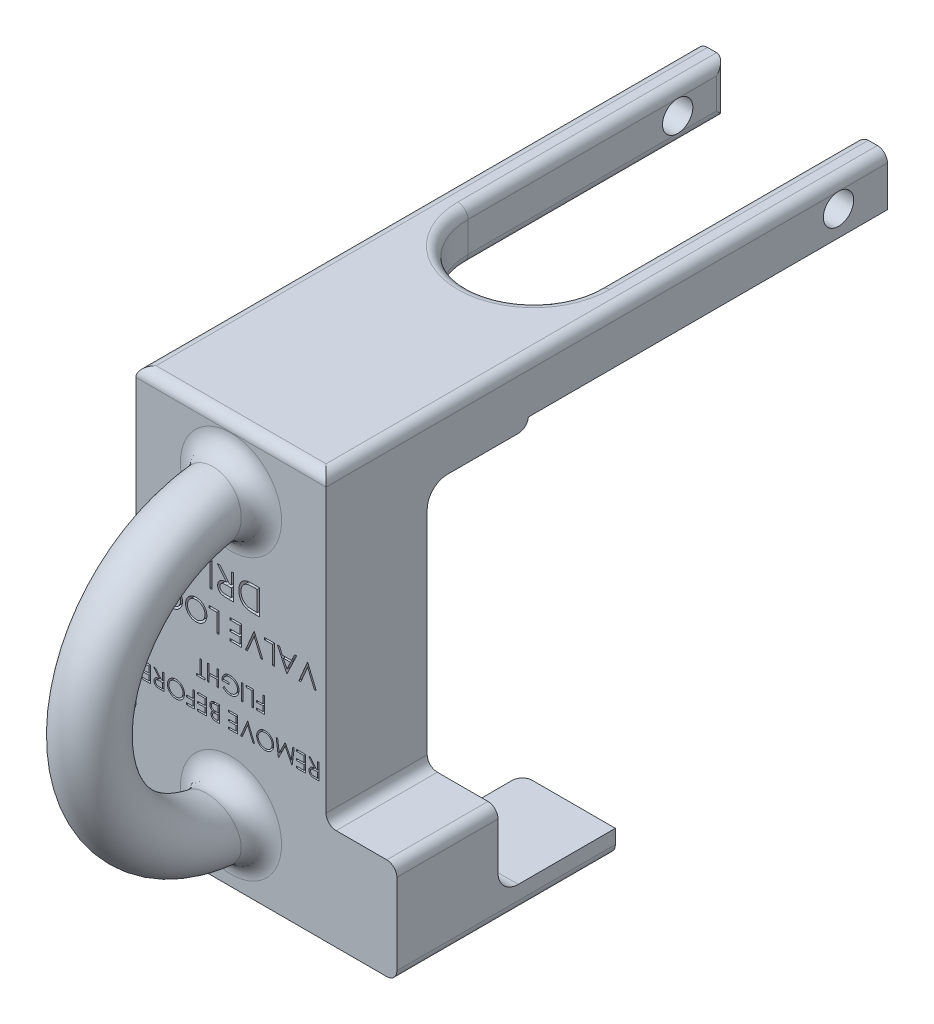
SolidWorks part; units mm, degrees
material "ABS PC"
ref_plane "Front Plane" through (0, 0, 0) normal (0, 0, 1) x (1, 0, 0)
ref_plane "Top Plane" through (0, 0, 0) normal (0, 1, 0) x (1, 0, 0)
ref_plane "Right Plane" through (0, 0, 0) normal (1, 0, 0) x (0, 0, -1)
sketch "Sketch1" plane through (0, 0, 0) normal (0, 0, 1) x (1, 0, 0)
  line L0 (0, 2.5) -> (0, -5) construction
  line L1 (-11.938, -5) -> (11.938, -5)
  line L2 (-11.938, -5) -> (-11.938, 2.5)
  line L3 (-11.938, 2.5) -> (11.938, 2.5)
  line L4 (11.938, -5) -> (11.938, 2.5)
  circle A0 centre (0, 0) radius 1.5
  dimension "D1" = 3
  dimension "D2" = 23.876
  dimension "D3" = 5
  dimension "D4" = 2.5
extrude "Boss-Extrude2" add sketch "Sketch1" along normal blind 25.4 contours L0 L3 L2 L1 A0 | L0 A0 | A0 L0 | L3 L0 A0 L1 L4
ref_plane "Plane1" through (0, -1.25, 0) normal (0, 1, 0) x (1, 0, 0)
sketch "Sketch15" plane through (0, 2.5, 0) normal (0, 1, 0) x (1, 0, 0)
  line L0 (-11.938, 0) -> (11.938, 0) construction
  line L1 (-11.938, 0) -> (11.938, 0)
  line L3 (-11.938, 0) -> (11.938, 0)
  line L7 (-8.255, 12.61) -> (8.255, 12.61) construction
  line L10 (-11.938, 0) -> (-11.938, 45.085)
  line L11 (-11.938, 45.085) -> (-8.255, 45.085)
  line L12 (-8.255, 12.61) -> (-8.255, 45.085)
  line L14 (8.255, 12.61) -> (8.255, 45.085)
  line L15 (8.255, 45.085) -> (11.938, 45.085)
  line L16 (11.938, 0) -> (11.938, 45.085)
  arc A0 (-8.255, 12.61) -> (8.255, 12.61) centre (0, 12.61) ccw
  dimension "D2" = 8.255
  dimension "D1" = 45.085
  dimension "D3" = 12.61
extrude "Boss-Extrude3" add sketch "Sketch15" against normal blind 6.35
sketch "Sketch19" plane through (0, -5, 0) normal (0, 1, 0) x (1, 0, 0)
  line L0 (-9.144, -20.32) -> (9.144, -20.32)
  line L1 (-11.938, -25.4) -> (11.938, -25.4) construction
  line L2 (-9.144, -20.32) -> (-9.144, -12.7)
  line L3 (-9.144, -12.7) -> (-11.938, -12.7)
  line L4 (-11.938, -25.4) -> (-11.938, 45.085) construction
  line L5 (-11.938, -12.7) -> (-11.938, -25.4)
  line L6 (-11.938, -25.4) -> (11.938, -25.4)
  line L7 (11.938, -25.4) -> (11.938, -12.7)
  line L8 (11.938, -25.4) -> (11.938, 45.085) construction
  line L9 (11.938, -12.7) -> (9.144, -12.7)
  line L10 (9.144, -12.7) -> (9.144, -20.32)
  point P10 (0, -20.32)
  point P17 (0, -25.4)
  dimension "D1" = 5.08
  dimension "D2" = 18.288
  dimension "D3" = 12.7
extrude "Boss-Extrude4" add sketch "Sketch19" against normal blind 43.18
sketch "Sketch20" plane through (11.938, 0, 0) normal (1, 0, 0) x (0, 0, -1)
  line L0 (45.085, -3.85) -> (45.085, 2.5) construction
  circle A0 centre (38.9382, -0.675) radius 1.905
  point P5 (45.085, -0.675)
  dimension "D2" = 3.81
  dimension "D1" = 6.1468
extrude "Cut-Extrude1" cut sketch "Sketch20" against normal through all
fillet "Fillet1" radius 2.54 2 edges at (9.144, -26.59, 20.32) (-9.144, -26.59, 20.32)
fillet "Fillet2" radius 2.54 2 edges at (-10.541, -5, 12.7) (10.541, -5, 12.7)
fillet "Fillet3" radius 2.54 5 edges at (9.144, -5, 13.97) (8.4001, -5, 19.5761) (0, -5, 20.32) (-8.4001, -5, 19.5761) (-9.144, -5, 13.97)
sketch "Sketch21" plane through (0, 0, 12.7) normal (0, 0, -1) x (-1, 0, 0)
  line L0 (11.938, -48.18) -> (11.938, -7.54) construction
  line L1 (9.144, -48.18) -> (11.938, -48.18)
  line L2 (9.144, -48.18) -> (9.144, -45.132)
  line L3 (9.144, -45.132) -> (11.938, -45.132)
  line L4 (11.938, -48.18) -> (11.938, -45.132)
  line L5 (-11.938, -48.18) -> (-11.938, -7.54) construction
  line L6 (-9.144, -48.18) -> (-11.938, -48.18)
  line L7 (-9.144, -48.18) -> (-9.144, -45.132)
  line L8 (-9.144, -45.132) -> (-11.938, -45.132)
  line L9 (-11.938, -48.18) -> (-11.938, -45.132)
  dimension "D1" = 3.048
extrude "Boss-Extrude5" add sketch "Sketch21" along normal blind 14.732
fillet "Fillet4" radius 2.54 2 edges at (-10.541, -45.132, 12.7) (10.541, -45.132, 12.7)
sketch "Sketch29" plane through (0, 0, 25.4) normal (0, 0, 1) x (1, 0, 0)
  line L0 (11.938, -29.13) -> (-11.938, -29.13) construction
  line L1 (11.938, -48.18) -> (11.938, 2.5) construction
  line L2 (-11.938, -48.18) -> (-11.938, 2.5) construction
  line L3 (11.938, -18.97) -> (-11.938, -18.97) construction
  line L4 (11.938, -25.32) -> (-11.938, -25.32) construction
  line L5 (11.938, -13.89) -> (-11.938, -13.89) construction
  line L6 (-11.938, -48.18) -> (11.938, -48.18) construction
  text T0 "REMOVE BEFORE" font "Century Gothic" height 2.032
  text T1 "FLIGHT" font "Century Gothic" height 2.032
  text T2 "VALVE LOCK" font "Century Gothic" height 2.54
  text T3 "DRL"
  dimension "D1" = 3.81
  dimension "D2" = 19.05
  dimension "D3" = 6.35
  dimension "D4" = 5.08
extrude "Cut-Extrude2" cut sketch "Sketch29" against normal blind 2.54
sketch "Sketch2" plane through (0, -25.38, 0) normal (1, 0, 0) x (0, -1, 0)
  line L1 (22.8, -25.4) -> (-27.88, -25.4) construction
  line L2 (22.8, -25.4) -> (-27.88, -25.4) construction
  arc A0 (-20.32, -25.4) -> (15.24, -25.4) centre (-2.54, -25.4) ccw
  dimension "D1" = 17.78
sweep "Sweep1" add path "Sketch2" circular profile diameter 7.62 parameters "D3"=7.62
fillet "Fillet6" radius 2.54 2 edges at (3.81, -5.06, 25.4) (3.81, -40.62, 25.4)
sketch "Sketch42" plane through (11.938, 0, 0) normal (1, 0, 0) x (0, 0, -1)
  line L0 (-25.4, -35.48) -> (-12.7, -35.48)
  line L10 (0, -5) -> (0, -3.85)
  line L11 (0, -3.85) -> (45.085, -3.85)
  line L12 (45.085, -3.85) -> (45.085, 2.5)
  line L13 (45.085, 2.5) -> (-25.4, 2.5)
  line L14 (-25.4, 2.5) -> (-25.4, -48.18)
  line L15 (-25.4, -48.18) -> (2.032, -48.18)
  line L16 (2.032, -48.18) -> (2.032, -45.132)
  line L17 (2.032, -45.132) -> (-10.16, -45.132)
  line L18 (-12.7, -42.592) -> (-12.7, -7.54)
  line L19 (-10.16, -5) -> (0, -5)
  line L24 (-25.4, -35.48) -> (-25.4, -48.18)
  line L25 (-25.4, -48.18) -> (2.032, -48.18)
  line L26 (2.032, -48.18) -> (2.032, -45.132)
  line L27 (2.032, -45.132) -> (-10.16, -45.132)
  line L28 (-12.7, -42.592) -> (-12.7, -35.48)
  arc A2 (-12.7, -42.592) -> (-10.16, -45.132) centre (-10.16, -42.592) ccw
  arc A3 (-10.16, -5) -> (-12.7, -7.54) centre (-10.16, -7.54) ccw
  arc A4 (-12.7, -42.592) -> (-10.16, -45.132) centre (-10.16, -42.592) ccw
  dimension "D2" = 12.7
  dimension "D1" = 0
extrude "Boss-Extrude6" add sketch "Sketch42" along normal blind 8.89
mirror "Mirror1" about plane through (0, 0, 0) normal (1, 0, 0) of "Boss-Extrude6"
fillet "Fillet7" radius 1.27 13 edges at (11.938, -35.48, 19.05) (20.828, -48.18, 11.684) (20.828, -35.48, 19.05) (-20.828, -35.48, 19.05) (-20.828, -48.18, 11.684) (-11.938, -35.48, 19.05) (-9.144, -46.656, -2.032) (9.144, -46.656, -2.032) (9.144, -48.18, 7.874) (0, -48.18, 20.32) (-9.144, -48.18, 7.874) (8.4001, -48.18, 19.5761) (-8.4001, -48.18, 19.5761)
fillet "Fillet8" radius 1.27 14 edges at (-11.938, 2.5, -9.8425) (11.938, 2.5, -9.8425) (0, 2.5, 25.4) (0, 2.5, -4.355) (8.255, 2.5, -28.8475) (8.255, -0.675, -45.085) (-8.255, -3.85, -28.8475) (-8.255, -0.675, -45.085) (0, -3.85, -4.355) (8.255, -3.85, -28.8475) (-8.255, 2.5, -28.8475) (0, -5, 0) (-11.938, -4.425, 0) (11.938, -4.425, 0)
